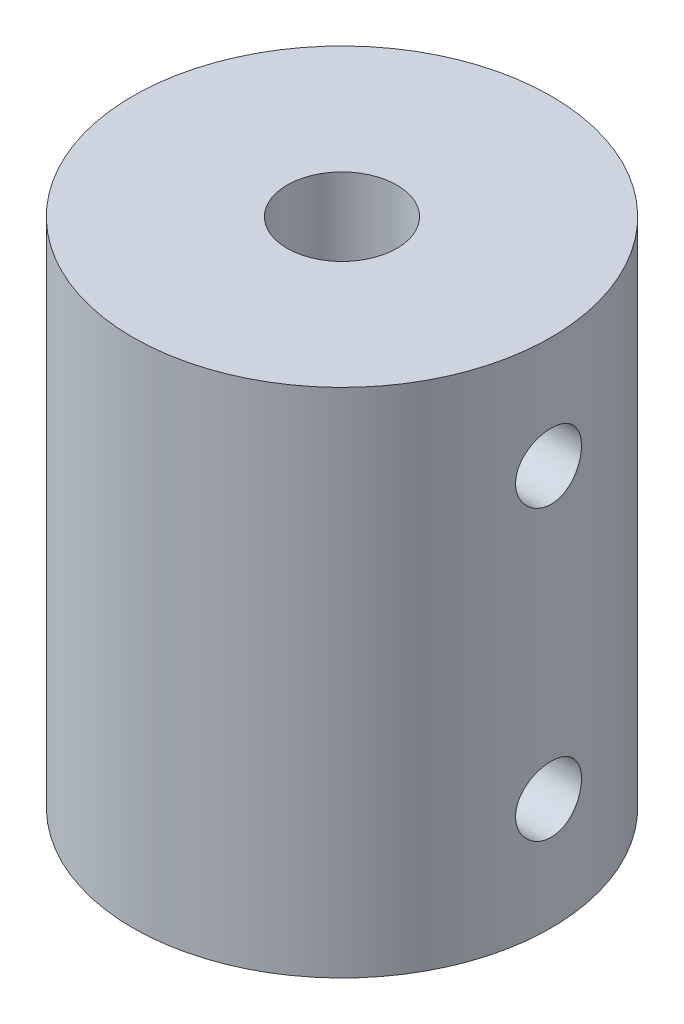
SolidWorks part; units mm, degrees
ref_plane "Front Plane" through (0, 0, 0) normal (0, 0, 1) x (1, 0, 0)
ref_plane "Top Plane" through (0, 0, 0) normal (0, 1, 0) x (1, 0, 0)
ref_plane "Right Plane" through (0, 0, 0) normal (1, 0, 0) x (0, 0, -1)
sketch "Sketch1" plane through (0, 0, 0) normal (0, 1, 0) x (1, 0, 0)
  circle A0 centre (0, 0) radius 9.525
  dimension "D1" = 19.05
extrude "Boss-Extrude1" add sketch "Sketch1" along normal blind 23.3
hole_wizard "Ø5.0mm Dowel Hole1" positions "Sketch2" profile "Sketch3" hole size "Ø5.0" standard "ANSI Metric" end condition through all
sketch "Sketch2" plane through (0, 23.3, 0) normal (0, 1, 0) x (1, 0, 0)
  point P0 (0, 0)
sketch "Sketch3" plane through (0, 23.3, 0) normal (1, 0, 0) x (0, 0, 1)
  line L0 (0, 0) -> (0, 23.3)
  line L1 (0, 23.3) -> (2.5, 23.3)
  line L2 (2.5, 23.3) -> (2.5, 0)
  line L5 (2.5, 0) -> (0, 0)
  line L11 (0, -6.35) -> (0, 107.95) construction
  dimension "Thru Hole Dia." = 5
  dimension "Thru Hole Depth" = 23.3
sketch "Sketch4" plane through (0, 0, 0) normal (1, 0, 0) x (0, 0, -1)
  line L0 (-9.525, 23.3) -> (-9.525, 0) construction
  line L1 (-9.525, 20.125) -> (-5.715, 20.125)
  line L2 (-9.525, 20.125) -> (-9.525, 3.175)
  line L3 (-9.525, 3.175) -> (-5.715, 3.175)
  line L4 (-5.715, 20.125) -> (-5.715, 3.175)
  line L5 (-9.525, 0) -> (9.525, 0) construction
  line L6 (9.525, 23.3) -> (-9.525, 23.3) construction
  line L7 (0, 0) -> (0, 26.8631) construction
  dimension "D1" = 3.175
  dimension "D2" = 3.175
  dimension "D3" = 3.81
ref_plane "Plane1" through (9.525, 0, 0) normal (1, 0, 0) x (0, 0, -1)
sketch "Sketch5" plane through (9.525, 0, 0) normal (1, 0, 0) x (0, 0, -1)
  line L0 (2.5, 23.3) -> (-2.5, 23.3) construction
  circle A0 centre (0, 18.22) radius 1.27
  circle A1 centre (0, 5.08) radius 1.27
  point P4 (0, 0)
  dimension "D3" = 2.54
  dimension "D1" = 5.08
  dimension "D2" = 5.08
hole_wizard "Ø3.0mm Dowel Hole1" positions "Sketch6" profile "Sketch7" hole size "Ø3.0" standard "ANSI Metric" end condition up to next
sketch "Sketch6" plane through (9.525, 0, 0) normal (1, 0, 0) x (0, 0, -1)
  point P0 (0, 18.22)
  point P3 (0, 5.08)
sketch "Sketch7" plane through (9.525, 18.22, 0) normal (0, 1, 0) x (0, 0, -1)
  line L0 (0, 0) -> (0, 7.025)
  line L1 (0, 7.025) -> (1.5, 7.025)
  line L2 (1.5, 7.025) -> (1.5, 0)
  line L5 (1.5, 0) -> (0, 0)
  line L11 (0, -6.35) -> (0, 107.95) construction
  dimension "Thru Hole Dia." = 3
  dimension "Thru Hole Depth" = 7.025
